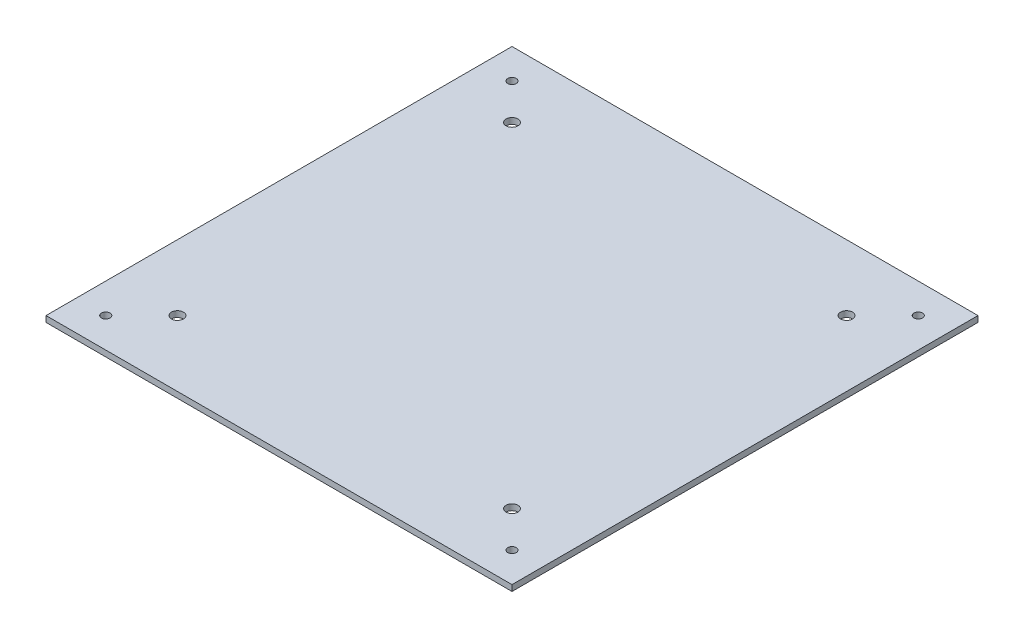
SolidWorks part; units mm, degrees
ref_plane "Front Plane" through (0, 0, 0) normal (0, 0, 1) x (1, 0, 0)
ref_plane "Top Plane" through (0, 0, 0) normal (0, 1, 0) x (1, 0, 0)
ref_plane "Right Plane" through (0, 0, 0) normal (1, 0, 0) x (0, 0, -1)
sketch "Sketch1" plane through (0, 0, 0) normal (0, 1, 0) x (1, 0, 0)
  line L1 (0, 0) -> (241.3, 0)
  line L2 (0, 0) -> (0, 241.3)
  line L3 (0, 241.3) -> (241.3, 241.3)
  line L4 (241.3, 0) -> (241.3, 241.3)
  dimension "9.5" = 241.3
  dimension "D2" = 241.3
extrude "Boss-Extrude1" add sketch "Sketch1" along normal blind 3.175
sketch "Sketch2" plane through (0, 3.175, 0) normal (0, 1, 0) x (1, 0, 0)
  line L0 (0, 0) -> (241.3, 0) construction
  line L1 (241.3, 0) -> (241.3, 241.3) construction
  line L2 (0, 0) -> (241.3, 241.3) construction
  circle A8 centre (209.55, 31.75) radius 3.175
  circle A9 centre (31.75, 31.75) radius 3.175
  circle A10 centre (31.75, 209.55) radius 3.175
  circle A11 centre (209.55, 209.55) radius 3.175
  circle A16 centre (228.6, 12.7) radius 2.286
  circle A17 centre (12.7, 12.7) radius 2.286
  circle A18 centre (12.7, 228.6) radius 2.286
  circle A19 centre (228.6, 228.6) radius 2.286
  point P10 (120.65, 120.65)
  dimension "D2" = 12.7
  dimension "D9" = 6.35
  dimension "D10" = 31.75
  dimension "D11" = 31.75
  dimension "D4" = 4.572
  dimension "D12" = 125.7236
  dimension "D13" = 177.8
  dimension "D3" = 12.7
  dimension "D5" = 4
  dimension "D7" = 215.9
  dimension "D8" = 152.6644
  dimension "D6" = 4
extrude "Cut-Extrude1" cut sketch "Sketch2" against normal through all
sketch "Sketch3" plane through (0, 3.175, 0) normal (0, 1, 0) x (1, 0, 0)
  line L0 (241.3, 0) -> (241.3, 241.3) construction
  line L1 (241.3, 241.3) -> (0, 241.3) construction
  line L2 (0, 241.3) -> (0, 0) construction
  line L3 (0, 0) -> (241.3, 0) construction
  line L4 (241.3, 0) -> (241.3, 241.3)
  line L5 (241.3, 241.3) -> (0, 241.3)
  line L6 (0, 241.3) -> (0, 0)
  line L7 (0, 0) -> (241.3, 0)
  line L8 (-3.175, 244.475) -> (-3.175, -3.175)
  line L9 (-3.175, -3.175) -> (244.475, -3.175)
  line L10 (244.475, -3.175) -> (244.475, 244.475)
  line L11 (244.475, 244.475) -> (-3.175, 244.475)
  dimension "D1" = 3.175
extrude "Boss-Extrude2" add sketch "Sketch3" against normal blind 3.175
